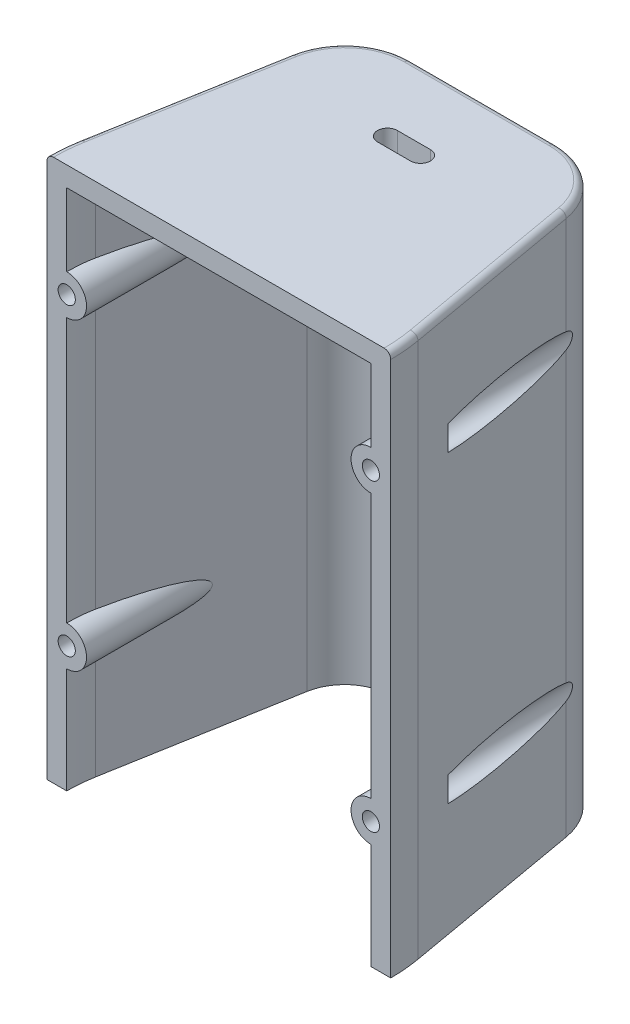
SolidWorks part; units mm, degrees
material "ABS"
ref_plane "Спереди" through (0, 0, 0) normal (0, 0, 1) x (1, 0, 0)
ref_plane "Сверху" through (0, 0, 0) normal (0, 1, 0) x (1, 0, 0)
ref_plane "Справа" through (0, 0, 0) normal (1, 0, 0) x (0, 0, -1)
sketch "Эскиз22" plane through (0, 0, 0) normal (0, 1, 0) x (1, 0, 0)
  line L0 (0, 0) -> (0, 37.9039) construction
  line L1 (-25.605, 4.5149) -> (-20.8051, 31.7365)
  line L2 (-10.957, 40) -> (0, 40)
  line L3 (-23, 0) -> (-26, 0)
  line L4 (-10.957, 37) -> (0, 37)
  line L5 (-22.6506, 3.9939) -> (-17.8507, 31.2155)
  line L6 (23, 0) -> (26, 0)
  line L7 (25.605, 4.5149) -> (20.8051, 31.7365)
  line L8 (22.6506, 3.9939) -> (17.8507, 31.2155)
  line L9 (10.957, 40) -> (0, 40)
  line L10 (10.957, 37) -> (0, 37)
  arc A0 (-25.605, 4.5149) -> (-26, 0) centre (0, 0) ccw
  arc A1 (-20.8051, 31.7365) -> (-10.957, 40) centre (-10.957, 30) cw
  arc A2 (-17.8507, 31.2155) -> (-10.957, 37) centre (-10.957, 30) cw
  arc A3 (-22.6506, 3.9939) -> (-23, 0) centre (0, 0) ccw
  arc A4 (22.6506, 3.9939) -> (23, 0) centre (0, 0) cw
  arc A5 (25.605, 4.5149) -> (26, 0) centre (0, 0) cw
  arc A6 (17.8507, 31.2155) -> (10.957, 37) centre (10.957, 30) ccw
  arc A7 (20.8051, 31.7365) -> (10.957, 40) centre (10.957, 30) ccw
  dimension "D1" = 26
  dimension "D2" = 10
  dimension "D3" = 10
  dimension "D5" = 40
  dimension "D4" = 3
extrude "Бобышка-Вытянуть1" add sketch "Эскиз22" along normal blind 82
sketch "Эскиз23" plane through (0, 82, 0) normal (0, 1, 0) x (1, 0, 0)
  line L0 (25.605, 4.5149) -> (20.8051, 31.7365) construction
  line L1 (-25.605, 4.5149) -> (-20.8051, 31.7365)
  line L2 (-20.8051, 31.7365) -> (-25.605, 4.5149) construction
  line L3 (20.8051, 31.7365) -> (25.605, 4.5149)
  line L4 (10.957, 40) -> (-10.957, 40)
  line L5 (-26, 0) -> (26, 0)
  arc A0 (26, 0) -> (25.605, 4.5149) centre (0, 0) ccw
  arc A1 (-20.8051, 31.7365) -> (-10.957, 40) centre (-10.957, 30) cw
  arc A2 (-10.957, 40) -> (-20.8051, 31.7365) centre (-10.957, 30) ccw construction
  arc A3 (10.957, 40) -> (20.8051, 31.7365) centre (10.957, 30) cw
  arc A4 (-26, 0) -> (-25.605, 4.5149) centre (0, 0) cw
extrude "Бобышка-Вытянуть2" add sketch "Эскиз23" against normal blind 3
sketch "Эскиз24" plane through (0, 0, 0) normal (0, 0, 1) x (1, 0, 0)
  line L0 (-23, 79) -> (-23, 0) construction
  line L6 (23, 79) -> (23, 0) construction
  circle A0 centre (-23, 65) radius 3
  circle A7 centre (23, 65) radius 3
  circle A8 centre (-23, 19) radius 3
  circle A9 centre (23, 19) radius 3
  dimension "D1" = 6
  dimension "D2" = 46
  dimension "D3" = 65
extrude "Бобышка-Вытянуть4" add sketch "Эскиз24" against normal up to surface (245.8774 mm away) contours A7 | A9 up to face at (20.2506, 39.5, -17.6047)
extrude "Бобышка-Вытянуть5" add sketch "Эскиз24<4>" against normal up to surface (19.0261 mm away) contours A0 | A8 up to face at (-20.2506, 39.5, -17.6047)
sketch "Эскиз24<4>" plane through (0, 0, 0) normal (0, 0, 1) x (1, 0, 0) same geometry as "Эскиз24"
fillet "Скругление1" radius 1 7 edges at (25.9011, 82, -2.266) (23.205, 82, -18.1257) (17.3849, 82, -37.6604) (0, 82, -40) (-17.3849, 82, -37.6604) (-23.205, 82, -18.1257) (-25.9011, 82, -2.266)
sketch "Эскиз27" plane through (0, 0, 0) normal (0, 0, 1) x (1, 0, 0)
  circle A0 centre (-23, 65) radius 1.3
  circle A1 centre (23, 65) radius 1.3
  circle A2 centre (23, 19) radius 1.3
  circle A3 centre (-23, 19) radius 1.3
  dimension "D1" = 2.6
extrude "Вырез-Вытянуть3" cut sketch "Эскиз27" against normal through all
sketch "Эскиз28" plane through (0, 0, 0) normal (0, 0, 1) x (1, 0, 0)
  circle A0 centre (-23, 65) radius 2.5
  circle A1 centre (23, 65) radius 2.5
  circle A2 centre (23, 19) radius 2.5
  circle A3 centre (-23, 19) radius 2.5
  dimension "D1" = 5
extrude "Вырез-Вытянуть4" cut sketch "Эскиз28" against normal through all from offset 10 offset against normal yes
sketch "Эскиз29" plane through (0, 82, 0) normal (0, 1, 0) x (1, 0, 0)
  line L0 (-2.5, 28) -> (2.5, 28) construction
  line L1 (-2.5, 29.5) -> (2.5, 29.5)
  line L2 (-2.5, 26.5) -> (2.5, 26.5)
  line L3 (-10.957, 40) -> (10.957, 40) construction
  arc A0 (-2.5, 29.5) -> (-2.5, 26.5) centre (-2.5, 28) ccw
  arc A1 (2.5, 26.5) -> (2.5, 29.5) centre (2.5, 28) ccw
  point P2 (0, 28)
  dimension "D2" = 1.5
  dimension "D1" = 12
  dimension "D3" = 5
extrude "Вырез-Вытянуть5" cut sketch "Эскиз29" against normal up to next
